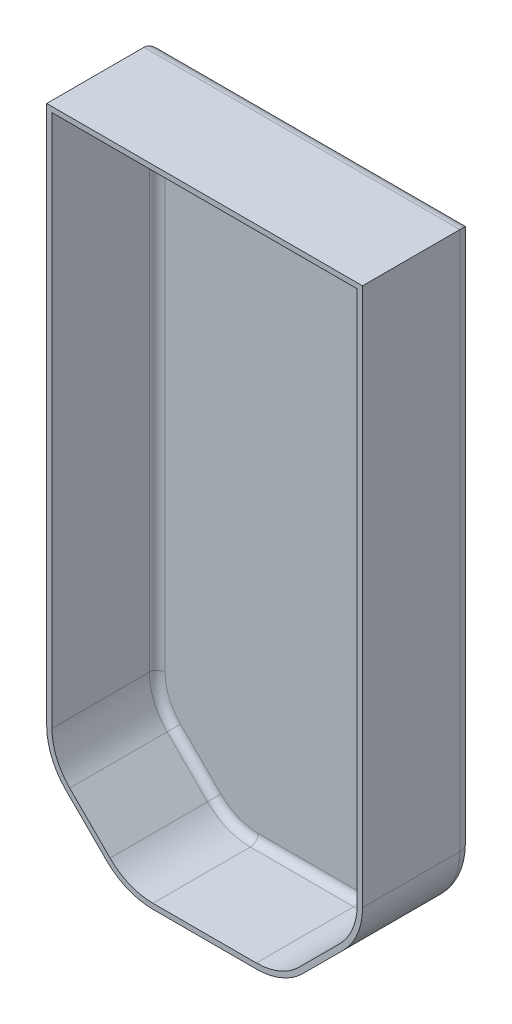
SolidWorks part; units mm, degrees
ref_plane "Front Plane" through (0, 0, 0) normal (0, 0, 1) x (1, 0, 0)
ref_plane "Top Plane" through (0, 0, 0) normal (0, 1, 0) x (1, 0, 0)
ref_plane "Right Plane" through (0, 0, 0) normal (1, 0, 0) x (0, 0, -1)
ref_axis "X" through (88.99, 0, 0) along (-1, 0, 0)
ref_axis "Y" through (0, 55, 0) along (0, -1, 0)
ref_axis "Z" through (0, 0, -88.99) along (0, 0, 1)
sketch "Sketch1" plane through (0, 0, 0) normal (0, 0, 1) x (1, 0, 0)
  line L0 (0, -50) -> (0, 0) construction
  line L1 (-60, 195) -> (60, 195)
  line L2 (-60, 195) -> (-60, -50)
  line L3 (-60, -50) -> (60, -50)
  line L4 (60, 195) -> (60, -50)
  dimension "D1" = 120
  dimension "D2" = 245
  dimension "D3" = 50
extrude "Boss-Extrude1" add sketch "Sketch1" along normal blind 42
chamfer "Chamfer1" distance 30 angle 45 2 edges at (-60, -50, 21) (60, -50, 21)
fillet "Fillet3" radius 25 4 edges at (-60, -20, 21) (-30, -50, 21) (30, -50, 21) (60, -20, 21)
fillet "Fillet1" radius 5 10 edges at (0, -50, 0) (60, 92.6777, 0) (0, 195, 0) (-60, 92.6777, 0) (-29.2117, -48.097, 0) (29.2117, -48.097, 0) (45, -35, 0) (58.097, -19.2117, 0) (-58.097, -19.2117, 0) (-45, -35, 0)
shell "Shell1" thickness 2 removed face at (0, 12.5738, 42)
